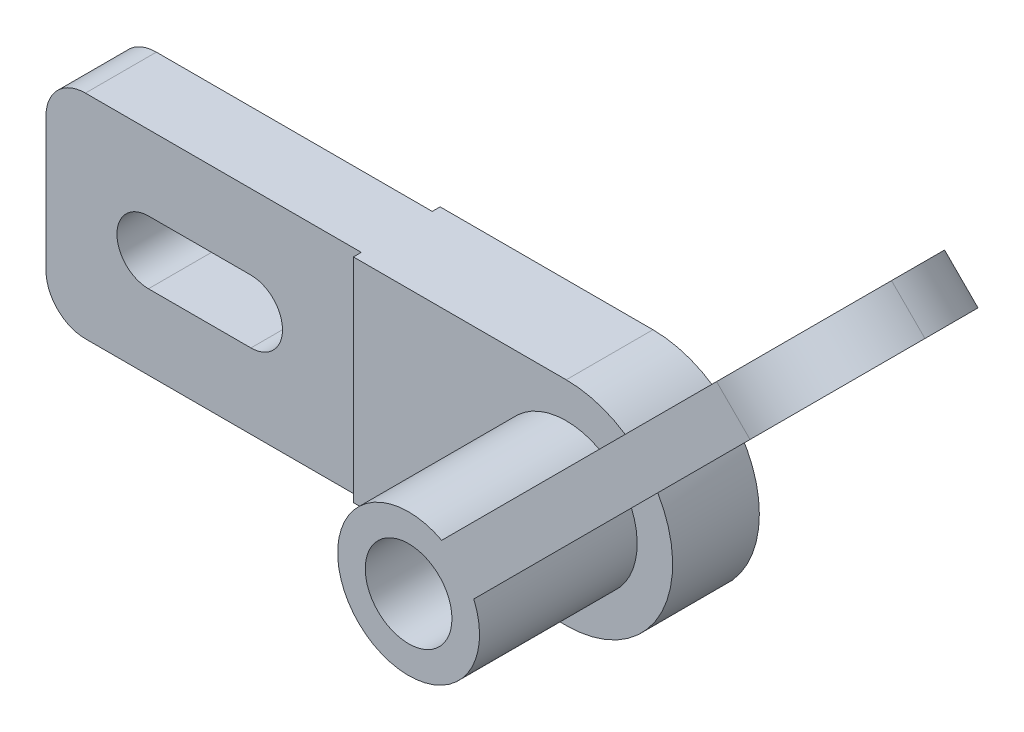
SolidWorks part; units mm, degrees
ref_plane "정면" through (0, 0, 0) normal (0, 0, 1) x (1, 0, 0)
ref_plane "윗면" through (0, 0, 0) normal (0, 1, 0) x (1, 0, 0)
ref_plane "우측면" through (0, 0, 0) normal (1, 0, 0) x (0, 0, -1)
sketch "스케치1" plane through (0, 0, 0) normal (0, 0, 1) x (1, 0, 0)
  line L1 (-67, 13.5) -> (0, 13.5)
  line L2 (-67, 13.5) -> (-67, -13.5)
  line L3 (-67, -13.5) -> (0, -13.5)
  arc A0 (0, -13.5) -> (0, 13.5) centre (0, 0) ccw
  point P0 (0, 0)
  point P7 (0, 0)
  dimension "D3" = 27
  dimension "D1" = 67
  dimension "D2" = 27
extrude "보스-돌출1" add sketch "스케치1" along normal blind 11
sketch "스케치2" plane through (0, 0, 11) normal (0, 0, 1) x (1, 0, 0)
  line L0 (-54, 0) -> (-41, 0) construction
  line L1 (-54, 4) -> (-41, 4)
  line L2 (-54, -4) -> (-41, -4)
  line L3 (-67, 13.5) -> (-67, -13.5) construction
  arc A0 (-54, 4) -> (-54, -4) centre (-54, 0) ccw
  arc A1 (-41, -4) -> (-41, 4) centre (-41, 0) ccw
  point P3 (-47.5, 0)
  dimension "D1" = 13
  dimension "D2" = 13
  dimension "D3" = 8
extrude "컷-돌출1" cut sketch "스케치2" against normal blind 15
sketch "스케치3" plane through (0, 0, 11) normal (0, 0, 1) x (1, 0, 0)
  circle A0 centre (0, 0) radius 9
  dimension "D1" = 18
extrude "보스-돌출2" add sketch "스케치3" along normal blind 20
sketch "스케치4" plane through (0, 0, 11) normal (0, 0, 1) x (1, 0, 0)
  line L0 (-27, 13.5) -> (-27, -13.5)
  line L1 (0, 13.5) -> (-67, 13.5) construction
  line L2 (-67, -13.5) -> (0, -13.5) construction
  line L3 (-67, 13.5) -> (-67, -13.5) construction
  line L4 (-27, 13.5) -> (-67, 13.5)
  line L5 (-67, 13.5) -> (-67, -13.5)
  line L6 (-67, -13.5) -> (-27, -13.5)
  dimension "D1" = 40
extrude "컷-돌출2" cut sketch "스케치4" against normal blind 1 contours L0 L6 L5 L4
ref_plane "평면1" through (0, 0, 5.5) normal (0, 0, 1) x (1, 0, 0)
mirror "대칭 복사1" about plane through (0, 0, 5.5) normal (0, 0, 1) of "컷-돌출2"
sketch "스케치6" plane through (0, 0, 31) normal (0, 0, 1) x (1, 0, 0)
  circle A0 centre (0, 0) radius 5.5
  dimension "D1" = 11
extrude "컷-돌출3" cut sketch "스케치6" against normal through all
sketch "스케치8" plane through (0, 0, 31) normal (0, 0, 1) x (1, 0, 0)
  line L0 (0, 0) -> (34.662, 0) construction
  line L1 (0, 0) -> (28.45, 28.45) construction
  line L2 (48.2671, 52.031) -> (3.0123, 6.7761)
  line L3 (48.2671, 52.031) -> (52.5098, 47.7883)
  line L4 (3.0123, 6.7761) -> (7.2549, 2.5335)
  line L5 (52.5098, 47.7883) -> (7.2549, 2.5335)
  line L6 (48.2671, 52.031) -> (7.2549, 2.5335) construction
  line L7 (3.0123, 6.7761) -> (52.5098, 47.7883) construction
  point P3 (0, 0)
  point P5 (27.761, 27.2822)
  point P6 (0, 0)
  dimension "D1" = 45
  dimension "D2" = 6
  dimension "D3" = 71
  dimension "D4" = 64
extrude "보스-돌출3" add sketch "스케치8" against normal blind 26
fillet "필렛1" radius 13 2 edges at (50.3885, 49.9096, 31) (50.3885, 49.9096, 5)
fillet "필렛2" radius 5 2 edges at (-67, -13.5, 5.5) (-67, 13.5, 5.5)
sketch "스케치11" plane through (2.3607, -2.3607, 0) normal (0.7071, -0.7071, 0) x (0, 0, -1)
  line L0 (-18, 58) -> (-18, 30) construction
  line L1 (-14, 58) -> (-14, 30)
  line L2 (-22, 58) -> (-22, 30)
  arc A0 (-14, 58) -> (-22, 58) centre (-18, 58) ccw
  arc A1 (-22, 30) -> (-14, 30) centre (-18, 30) ccw
  point P3 (-18, 44)
  point P8 (-18, 62)
  point P9 (0, 0)
  dimension "D1" = 4
  dimension "D2" = 28
  dimension "D3" = 58
extrude "컷-돌출4" cut sketch "스케치11" against normal blind 10
